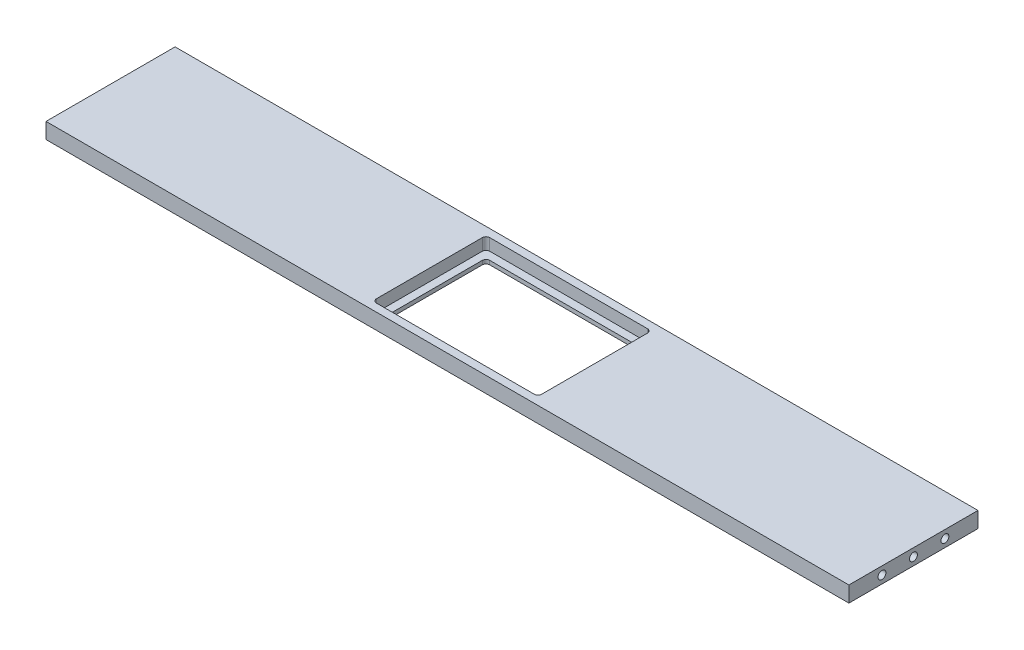
SolidWorks part; units mm, degrees
material "6061 Alloy"
ref_plane "Front" through (0, 0, 0) normal (0, 0, 1) x (1, 0, 0)
ref_plane "Top" through (0, 0, 0) normal (0, 1, 0) x (1, 0, 0)
ref_plane "Right" through (0, 0, 0) normal (1, 0, 0) x (0, 0, -1)
sketch "Sketch2" plane through (0, 0, 0) normal (0, 0, 1) x (1, 0, 0)
  line L5 (0, -12.7) -> (0, 0) construction
  line L9 (-323.85, -12.7) -> (-323.85, 0)
  line L11 (323.85, -12.7) -> (323.85, 0)
  line L15 (-323.85, -12.7) -> (323.85, -12.7)
  line L17 (-323.85, 0) -> (323.85, 0)
  dimension "D3" = 647.7
  dimension "D4" = 12.7
extrude "Boss-Extrude1" add sketch "Sketch2" along normal mid plane 104.14
sketch "Sketch3" plane through (0, 0, 0) normal (0, 1, 0) x (1, 0, 0)
  line L0 (0, -45.72) -> (0, -39.37) construction
  line L1 (63.675, 45.72) -> (-63.675, 45.72)
  line L2 (66.675, 42.72) -> (66.675, -42.72)
  line L3 (63.675, -45.72) -> (-63.675, -45.72)
  line L4 (-66.675, 42.72) -> (-66.675, -42.72)
  line L5 (66.675, 45.72) -> (-66.675, -45.72) construction
  line L6 (66.675, -45.72) -> (-66.675, 45.72) construction
  line L7 (57.325, 39.37) -> (-57.325, 39.37)
  line L8 (60.325, 36.37) -> (60.325, -36.37)
  line L9 (57.325, -39.37) -> (-57.325, -39.37)
  line L10 (-60.325, 36.37) -> (-60.325, -36.37)
  line L11 (0, 39.37) -> (0, 45.72) construction
  arc A0 (63.675, 45.72) -> (66.675, 42.72) centre (63.675, 42.72) cw
  arc A1 (-66.675, 42.72) -> (-63.675, 45.72) centre (-63.675, 42.72) cw
  arc A2 (-63.675, -45.72) -> (-66.675, -42.72) centre (-63.675, -42.72) cw
  arc A3 (66.675, -42.72) -> (63.675, -45.72) centre (63.675, -42.72) cw
  arc A4 (57.325, 39.37) -> (60.325, 36.37) centre (57.325, 36.37) cw
  arc A5 (-57.325, 39.37) -> (-60.325, 36.37) centre (-57.325, 36.37) ccw
  arc A6 (-57.325, -39.37) -> (-60.325, -36.37) centre (-57.325, -36.37) cw
  arc A7 (60.325, -36.37) -> (57.325, -39.37) centre (57.325, -36.37) cw
  point P0 (0, 0)
  point P18 (0, 0)
  dimension "D3" = 3
  dimension "D6" = 3
  dimension "D1" = 133.35
  dimension "D2" = 91.44
  dimension "D4" = 6.35
  dimension "D5" = 6.35
  dimension "D7" = 6.35
extrude "Cut-Extrude1" cut sketch "Sketch3" against normal offset from surface (9.525 mm away) 3.175 contours L3 A2 L4 A1 L1 A0 L2 A3 up to face at (0, -12.7, 0)
hole_wizard "1/4\"-20 threaded hole" positions "Sketch7" profile "Sketch6" hole size "#97" standard "ANSI Inch"
sketch "Sketch7" plane through (-323.85, 0, 0) normal (-1, 0, 0) x (0, 0, 1)
  line L0 (-52.07, -6.35) -> (52.07, -6.35) construction
  line L1 (-52.07, 0) -> (-52.07, -12.7) construction
  line L2 (52.07, 0) -> (52.07, -12.7) construction
  point P0 (-25.4, -6.35)
  point P2 (0, -6.35)
  point P4 (25.4, -6.35)
  dimension "D1" = 25.4
  dimension "D2" = 25.4
sketch "Sketch6" plane through (-323.85, -6.35, -25.4) normal (0, 1, 0) x (0, 0, 1)
  line L0 (0, 0) -> (0, 52.7077)
  line L1 (0, 52.7077) -> (3.175, 50.8)
  line L2 (3.175, 50.8) -> (3.175, 0)
  line L5 (3.175, 0) -> (0, 0)
  line L10 (0, 52.7077) -> (-3.175, 50.8) construction
  line L11 (0, -6.35) -> (0, 107.95) construction
  dimension "Hole Dia." = 6.35
  dimension "Hole Depth" = 50.8
  dimension "Drill Angle" = 118
mirror "Mirror1" about plane through (0, 0, 0) normal (1, 0, 0) of "1/4\"-20 threaded hole"
extrude "Cut-Extrude2" cut sketch "Sketch3<3>" against normal through all contours L9 A6 L10 A5 L7 A4 L8 A7
sketch "Sketch3<3>" plane through (0, 0, 0) normal (0, 1, 0) x (1, 0, 0) same geometry as "Sketch3"
